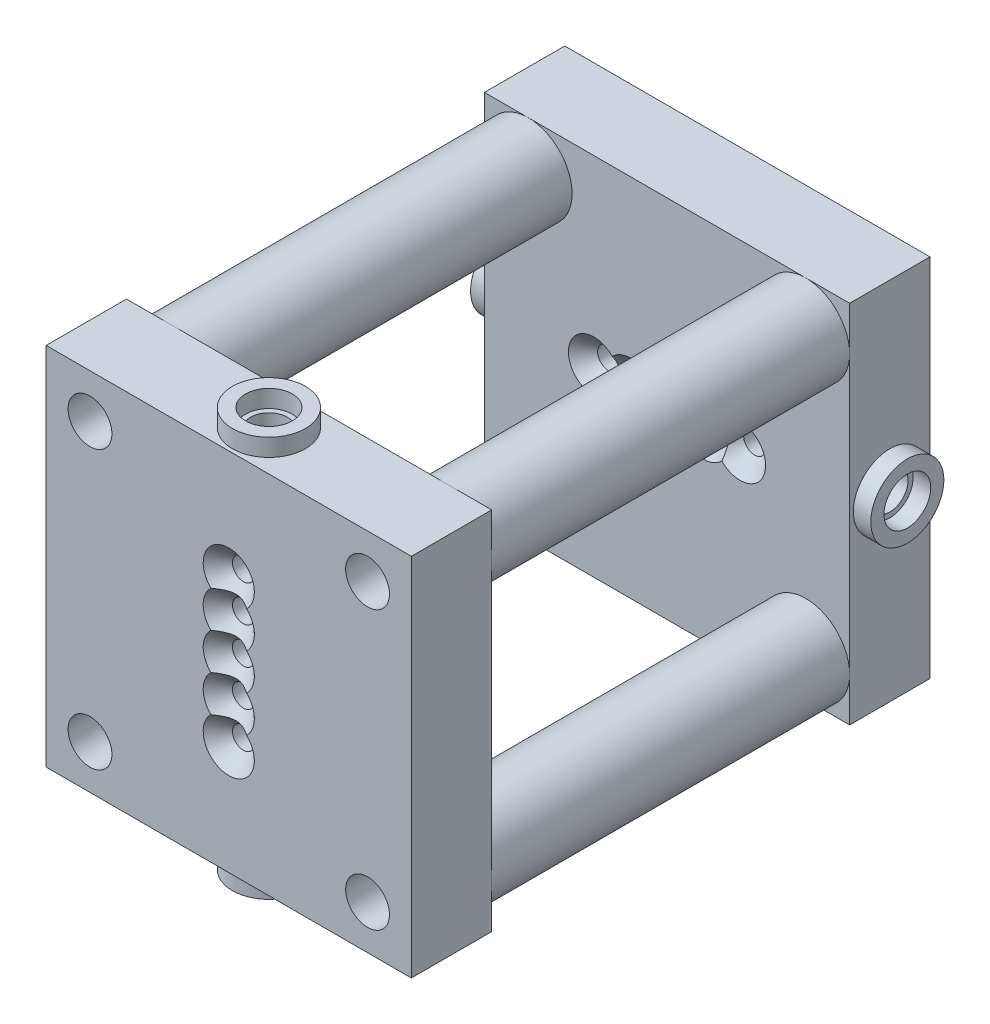
SolidWorks part; units mm, degrees
material "ﾎﾟﾘｵｷｼﾒﾁﾚﾝ(POM)ｱｾﾀｰﾙ共重合体"
ref_plane "正面" through (0, 0, 0) normal (0, 0, 1) x (1, 0, 0)
ref_plane "平面" through (0, 0, 0) normal (0, 1, 0) x (1, 0, 0)
ref_plane "右側面" through (0, 0, 0) normal (1, 0, 0) x (0, 0, -1)
sketch "ｽｹｯﾁ1" plane through (0, 0, 0) normal (0, 0, 1) x (1, 0, 0)
  line L0 (0, 0) -> (0, -12.5) construction
  line L1 (-12.5, 12.5) -> (12.5, 12.5)
  line L2 (-12.5, 12.5) -> (-12.5, -12.5)
  line L3 (-12.5, -12.5) -> (12.5, -12.5)
  line L4 (12.5, 12.5) -> (12.5, -12.5)
  line L5 (-12.5, 12.5) -> (12.5, -12.5) construction
  line L6 (-12.5, -12.5) -> (12.5, 12.5) construction
  circle A0 centre (0, 0) radius 0.75
  circle A1 centre (2.5, 0) radius 0.75
  circle A2 centre (5, 0) radius 0.75
  circle A3 centre (-5, 0) radius 0.75
  circle A4 centre (-2.5, 0) radius 0.75
  point P0 (0, 0)
  dimension "D2" = 1.5
  dimension "D1" = 25
  dimension "D4" = 10
  dimension "D3" = 3
extrude "ﾎﾞｽ - 押し出し1" add sketch "ｽｹｯﾁ1" along normal blind 5.5
hole_wizard "M3x0.5 ねじ穴1" positions "ｽｹｯﾁ15" profile "ｽｹｯﾁ16" tap size "M3x0.5" standard "JIS"
sketch "ｽｹｯﾁ15" plane through (-12.5, 0, 0) normal (-1, 0, 0) x (0, 0, 1)
  line L0 (2.75, -12.5) -> (2.75, 0) construction
  line L1 (5.5, -12.5) -> (0, -12.5) construction
  line L2 (2.75, 0) -> (0, 0) construction
  line L3 (0, 12.5) -> (0, -12.5) construction
  point P0 (2.75, 0)
sketch "ｽｹｯﾁ16" plane through (-12.5, 0, 2.75) normal (0, 1, 0) x (0, 0, 1)
  line L0 (0, 0) -> (0, 5.7511)
  line L1 (0, 5.7511) -> (1.25, 5)
  line L2 (1.25, 5) -> (1.25, 0)
  line L5 (1.25, 0) -> (0, 0)
  line L10 (0, 5.7511) -> (-1.25, 5) construction
  line L11 (0, -6.35) -> (0, 107.95) construction
  dimension "ねじ下穴ﾄﾞﾘﾙ直径" = 2.5
  dimension "ねじ下穴ﾄﾞﾘﾙの深さ" = 5
  dimension "ﾄﾞﾘﾙ角度" = 118
cosmetic thread "穴のねじ山1" parameters "D1"=6, "D2"=3
sketch "ｽｹｯﾁ17" plane through (-12.5, 0, 0) normal (-1, 0, 0) x (0, 0, 1)
  circle A0 centre (2.75, 0) radius 1.6
  circle A1 centre (2.75, 0) radius 2.5
  dimension "D1" = 3.2
  dimension "D2" = 5
extrude "ﾎﾞｽ - 押し出し3" add sketch "ｽｹｯﾁ17" along normal blind 1.2 separate body
chamfer "面取り1" distance 1 angle 45 10 edges at (5.75, 0, 5.5) (3.25, 0, 5.5) (0.75, 0, 5.5) (-3.25, 0, 5.5) (-5.75, 0, 5.5) (-5.75, 0, 0) (-3.25, 0, 0) (0.75, 0, 0) (3.25, 0, 0) (5.75, 0, 0)
mirror "ﾐﾗｰ1" about plane through (0, 0, 0) normal (1, 0, 0) of "M3x0.5 ねじ穴1"
mirror "ﾐﾗｰ2" about plane through (0, 0, 0) normal (1, 0, 0) of bodies 113
pattern_linear "直線ﾊﾟﾀｰﾝ1" count 2 spacing 30 along (0, 0, 1) of bodies 116 113 112 101
move or copy body "ﾎﾞﾃﾞｨ-移動/ｺﾋﾟｰ1" bodies to move or copy 102 117 118 copy no rotation origin (0, 0, 0) rotation axis (0, 0, 1) rotation angle 90
hole_wizard "M3 すきま穴1" positions "ｽｹｯﾁ2" profile "ｽｹｯﾁ3" hole size "M3" standard "JIS" end condition through all
sketch "ｽｹｯﾁ2" plane through (0, 0, 35.5) normal (0, 0, 1) x (1, 0, 0)
  line L1 (-9.5, 9.5) -> (9.5, 9.5)
  line L2 (-9.5, 9.5) -> (-9.5, -9.5)
  line L3 (-9.5, -9.5) -> (9.5, -9.5)
  line L4 (9.5, 9.5) -> (9.5, -9.5)
  line L5 (-9.5, 9.5) -> (9.5, -9.5) construction
  line L7 (12.5, 12.5) -> (-12.5, 12.5) construction
  point P0 (9.5, 9.5)
  point P2 (9.5, -9.5)
  point P4 (-9.5, -9.5)
  point P6 (-9.5, 9.5)
  dimension "D1" = 3
sketch "ｽｹｯﾁ3" plane through (9.5, 9.5, 35.5) normal (1, 0, 0) x (0, -1, 0)
  line L0 (0, 0) -> (0, 35.7429)
  line L1 (0, 35.7429) -> (1.5, 35.7429)
  line L2 (1.5, 35.7429) -> (1.5, 0)
  line L5 (1.5, 0) -> (0, 0)
  line L11 (0, -6.35) -> (0, 107.95) construction
  dimension "通し穴の直径" = 3
  dimension "通し穴の深さ" = 35.7429
sketch "ｽｹｯﾁ4" plane through (0, 0, 5.5) normal (0, 0, 1) x (1, 0, 0)
  circle A0 centre (9.5, 9.5) radius 1.5 construction
  circle A1 centre (9.5, -9.5) radius 1.5 construction
  circle A2 centre (-9.5, -9.5) radius 1.5 construction
  circle A3 centre (-9.5, 9.5) radius 1.5 construction
  circle A4 centre (9.5, 9.5) radius 1.5
  circle A5 centre (9.5, -9.5) radius 1.5
  circle A6 centre (-9.5, -9.5) radius 1.5
  circle A7 centre (-9.5, 9.5) radius 1.5
  circle A8 centre (9.5, 9.5) radius 3
  circle A9 centre (9.5, -9.5) radius 3
  circle A10 centre (-9.5, -9.5) radius 3
  circle A11 centre (-9.5, 9.5) radius 3
  dimension "D1" = 1.5
extrude "ﾎﾞｽ - 押し出し2" add sketch "ｽｹｯﾁ4" along normal up to surface (24.5 mm away) separate body up to face at (11, 9.5, 30)
sketch3d "3Dｽｹｯﾁ1"
  line L0 (-5, 0, 5.5) -> (0, -5, 30)
  line L1 (-5, 0, 4.5) -> (-5, 0, 1) construction
  line L2 (0, -5, 34.5) -> (0, -5, 31) construction
  line L3 (-2.5, 0, 5.5) -> (0, -2.5, 30)
  line L4 (-2.5, 0, 4.5) -> (-2.5, 0, 1) construction
  line L5 (0, -2.5, 34.5) -> (0, -2.5, 31) construction
  line L6 (0, 0, 5.5) -> (0, 0, 30)
  line L7 (0, 0, 4.5) -> (0, 0, 1) construction
  line L8 (0, 0, 34.5) -> (0, 0, 31) construction
  line L9 (2.5, 0, 5.5) -> (0, 2.5, 30)
  line L10 (2.5, 0, 4.5) -> (2.5, 0, 1) construction
  line L11 (0, 2.5, 34.5) -> (0, 2.5, 31) construction
  line L12 (5, 0, 5.5) -> (0, 5, 30)
  line L13 (5, 0, 4.5) -> (5, 0, 1) construction
  line L14 (0, 5, 34.5) -> (0, 5, 31) construction
sketch "ｽｹｯﾁ18" plane through (0, 0, 0) normal (1, 0, 0) x (0, 0, -1)
  line L0 (-30, 5) -> (-32.75, 5)
  line L1 (-35.5, 12.5) -> (-30, 12.5) construction
  line L2 (-30, 2.5) -> (-32.75, 2.5)
  line L3 (-30, 0) -> (-32.75, 0)
  line L4 (-30, -2.5) -> (-32.75, -2.5)
  line L5 (-30, -5) -> (-32.75, -5)
  point P6 (-32.75, 12.5)
  dimension "D1" = 5
sketch "ｽｹｯﾁ19" plane through (0, 0, 0) normal (0, 1, 0) x (1, 0, 0)
  line L0 (-5, -5.5) -> (-5, -2.75)
  line L1 (-2.5, -5.5) -> (-2.5, -2.75)
  line L2 (0, -5.5) -> (0, -2.75)
  line L3 (2.5, -5.5) -> (2.5, -2.75)
  line L4 (5, -5.5) -> (5, -2.75)
  line L5 (12.5, -5.5) -> (-12.5, -5.5) construction
  line L6 (5, -5.5) -> (0, -30) construction
  dimension "D1" = 5
